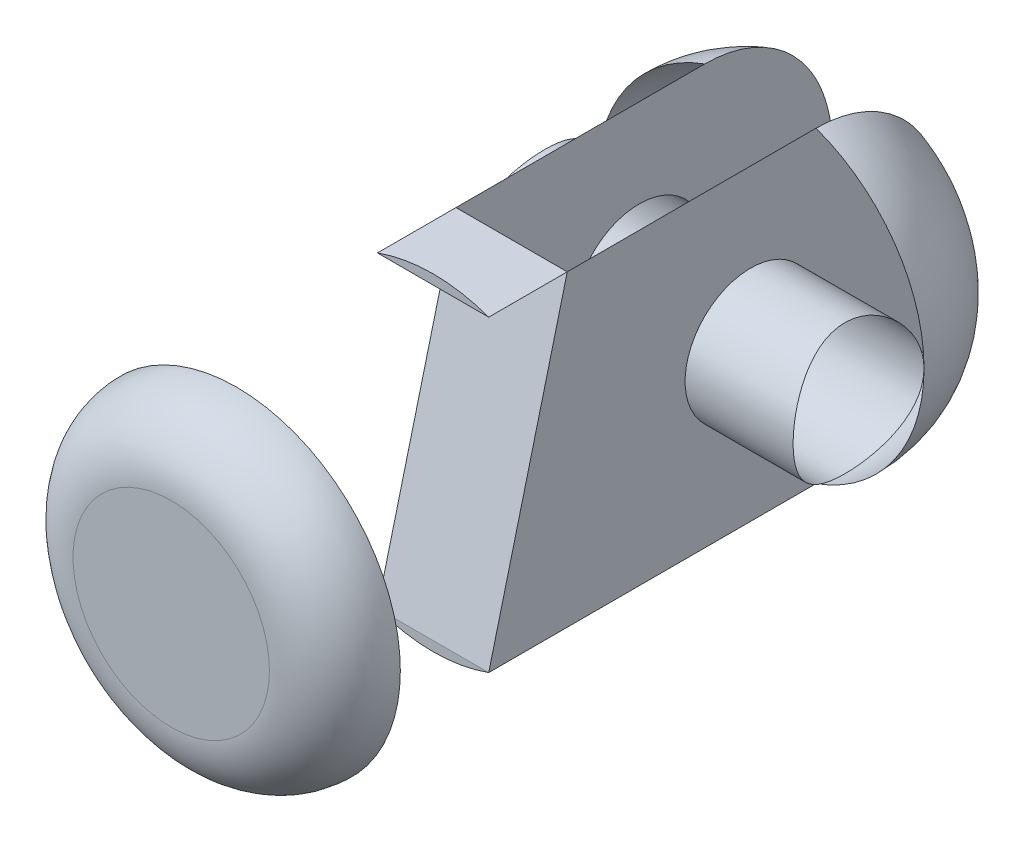
SolidWorks part; units mm, degrees
ref_plane "Plan de face" through (0, 0, 0) normal (0, 0, 1) x (1, 0, 0)
ref_plane "Plan de dessus" through (0, 0, 0) normal (0, 1, 0) x (1, 0, 0)
ref_plane "Plan de droite" through (0, 0, 0) normal (1, 0, 0) x (0, 0, -1)
sketch "Esquisse1" plane through (0, 0, 0) normal (0, 0, 1) x (1, 0, 0)
  circle A0 centre (0, 0) radius 2.5
  dimension "D1" = 5
extrude "Boss.-Extru.1" add sketch "Esquisse1" along normal blind 4
sketch "Esquisse2" plane through (0, 0, 0) normal (0, 0, -1) x (-1, 0, 0)
  line L0 (0.85, -2.3511) -> (0.85, 2.3511)
  line L1 (0, -2.5) -> (0, 2.5) construction
  line L2 (-0.85, -2.3511) -> (-0.85, 2.3511)
  arc A0 (0.85, -2.3511) -> (0.85, 2.3511) centre (0, 0) ccw
  circle A1 centre (0, 0) radius 2.5 construction
  arc A2 (-0.85, -2.3511) -> (-0.85, 2.3511) centre (0, 0) cw
  dimension "D1" = 1.7
extrude "Boss.-Extru.2" add sketch "Esquisse2" along normal blind 7
sketch "Esquisse3" plane through (0.85, 0, 0) normal (-1, 0, 0) x (0, 0, 1)
  line L0 (-7, -2.3511) -> (-7, 2.3511) construction
  circle A0 centre (-4, 0) radius 1
  point P4 (-7, 0)
  dimension "D1" = 2
  dimension "D2" = 0
  dimension "D3" = 3
extrude "Enlèv. mat.-Extru.2" cut sketch "Esquisse3" against normal through all both and the other way through all
fillet "Congé1" radius 2 2 edges at (-2.5, 0, -7) (2.5, 0, -7)
sketch "Esquisse4" plane through (-0.85, 0, 0) normal (1, 0, 0) x (0, 0, -1)
  line L0 (0, -2.3511) -> (1.2, 2.3511)
  line L2 (5, 2.3511) -> (0, 2.3511) construction
  line L3 (0, -2.3511) -> (0, 2.3511)
  line L4 (1.2, 2.3511) -> (0, 2.3511)
  dimension "D1" = 1.2
extrude "Boss.-Extru.3" add sketch "Esquisse4" along normal up to next
fillet "Congé2" radius 1 1 edges at (2.5, 0, 4)
